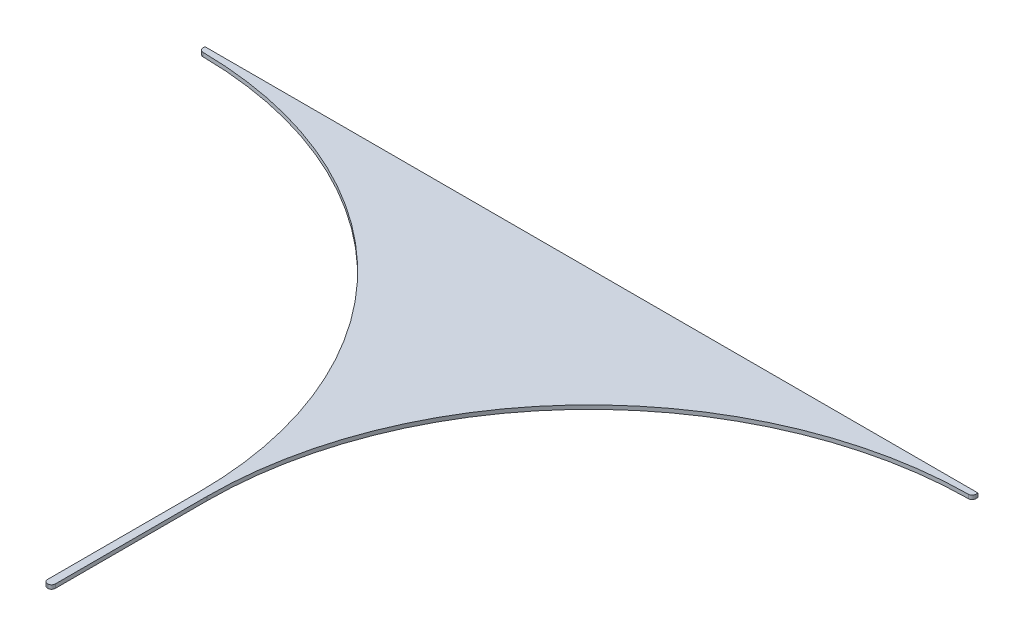
SolidWorks part; units mm, degrees
material "Galvanized Steel"
ref_plane "Front Plane" through (0, 0, 0) normal (0, 0, 1) x (1, 0, 0)
ref_plane "Top Plane" through (0, 0, 0) normal (0, 1, 0) x (1, 0, 0)
ref_plane "Right Plane" through (0, 0, 0) normal (1, 0, 0) x (0, 0, -1)
sketch "Sketch1" plane through (0, 0, 0) normal (0, 1, 0) x (1, 0, 0)
  line L0 (0, 0) -> (398, 0)
  line L2 (199, -280) -> (199.1, -280)
  line L3 (199, -280) -> (198.9, -280)
  line L4 (201, -278.1) -> (201, -200)
  line L5 (197, -278.1) -> (197, -200)
  line L6 (398, 0) -> (398, -1.1091)
  line L8 (0, -1.1091) -> (0, 0)
  arc A0 (396.1181, -3.009) -> (201, -200) centre (398, -200) ccw
  arc A1 (197, -200) -> (1.8819, -3.009) centre (0, -200) ccw
  arc A2 (197, -278.1) -> (198.9, -280) centre (198.9, -278.1) ccw
  arc A3 (199.1, -280) -> (201, -278.1) centre (199.1, -278.1) ccw
  arc A4 (0, -1.1091) -> (1.8819, -3.009) centre (1.9, -1.1091) ccw
  arc A5 (396.1181, -3.009) -> (398, -1.1091) centre (396.1, -1.1091) ccw
  point P18 (0, -3)
  point P21 (398, -3)
  dimension "D1" = 1.9
  dimension "D2" = 1.9
base flange "Base-Flange1" sketch "Sketch1" thickness 2 reverse thickness direction no parameters "D1"=10
sketch "Bend-Lines1" [suppressed] plane through (0, 0, 0) normal (0, 1, 0) x (1, 0, 0)
sketch "Bounding-Box1" [suppressed] plane through (0, 0, 0) normal (0, 1, 0) x (1, 0, 0)
sheet metal parameters "Sheet-Metal1" thickness 2 parameters "D1"=10
flat pattern "Flat-Pattern1" [suppressed]
sketch "Bend-Lines2" plane through (0, 0, 0) normal (0, 1, 0) x (1, 0, 0)
sketch3d "Bounding-Box2" [suppressed]
  line L0 (-1.9, -278.8909, 0) -> (396.1, -278.8909, 0) construction
  line L1 (-1.9, 1.1091, 0) -> (396.1, 1.1091, 0) construction
  line L2 (-1.9, -278.8909, 0) -> (-1.9, 1.1091, 0) construction
  line L3 (396.1, -278.8909, 0) -> (396.1, 1.1091, 0) construction
